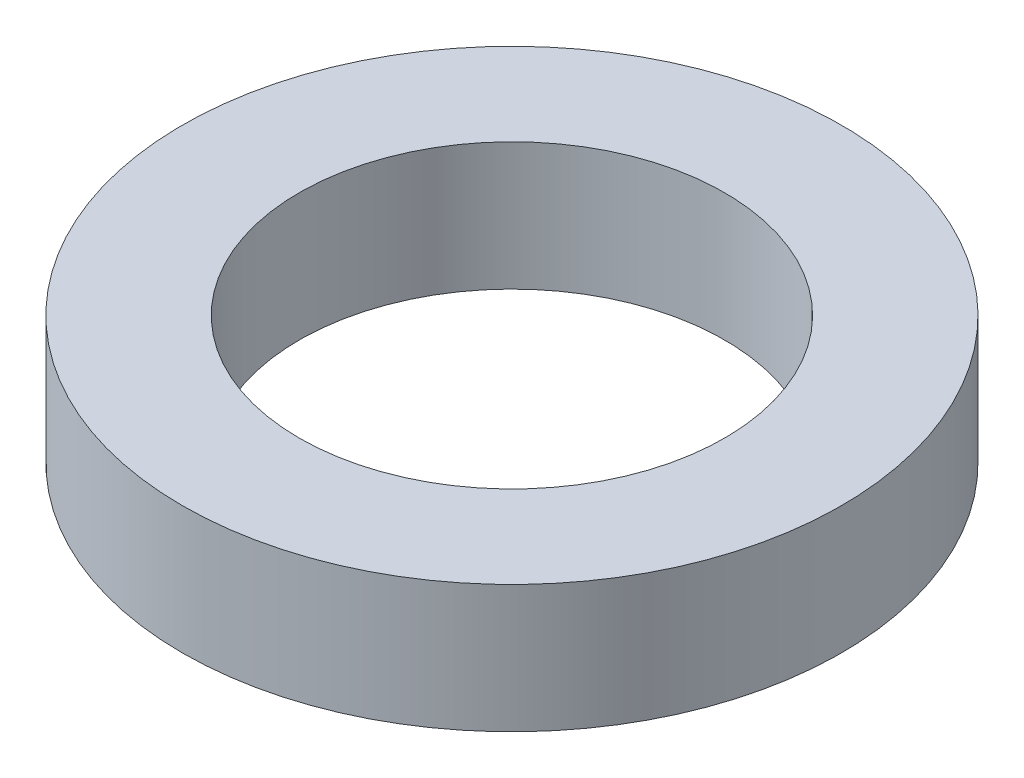
SolidWorks part; units mm, degrees
ref_plane "Front Plane" through (0, 0, 0) normal (0, 0, 1) x (1, 0, 0)
ref_plane "Top Plane" through (0, 0, 0) normal (0, 1, 0) x (1, 0, 0)
ref_plane "Right Plane" through (0, 0, 0) normal (1, 0, 0) x (0, 0, -1)
other "Bounding Box"
ref_plane "Default Plane" through (-8.9266, -12.7485, 0) normal (-0.1736, 0.9848, 0) x (0.9848, 0.1736, 0)
sketch "Sketch1" plane through (0, 0, 0) normal (0, 1, 0) x (1, 0, 0)
  circle A0 centre (0, 0) radius 20
  circle A1 centre (0, 0) radius 31
  dimension "D1" = 40
  dimension "D2" = 62
extrude "Boss-Extrude1" add sketch "Sketch1" along normal mid plane 12
